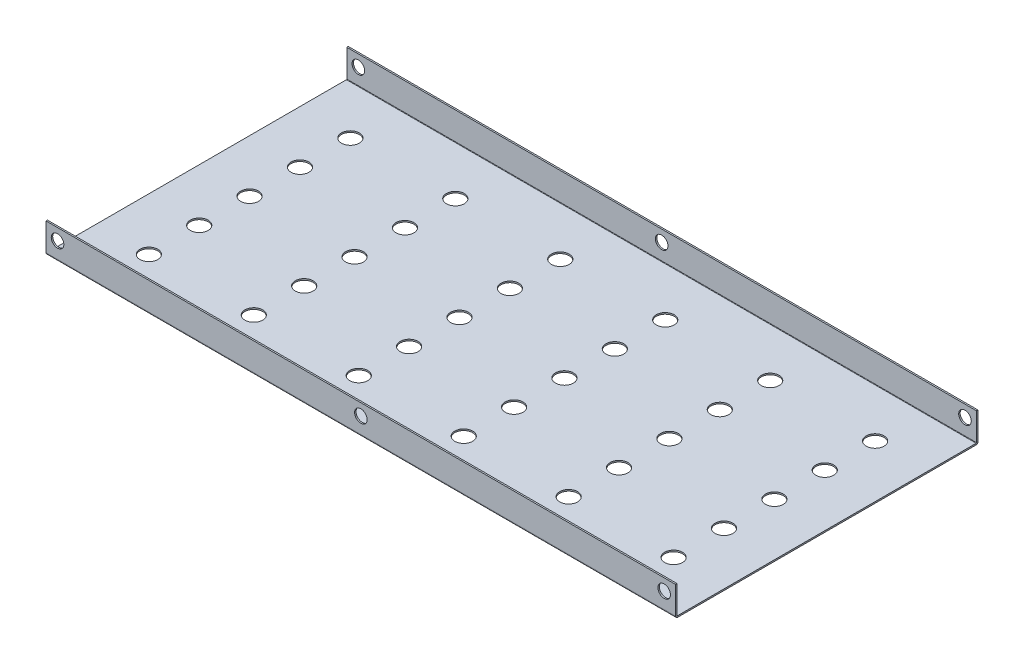
SolidWorks part; units mm, degrees
note: The reader was unsure of these and kept them because the rebuilt part matched: flange length of "边线-法兰1".
material "1023 碳钢板 (SS)"
ref_plane "前视基准面" through (0, 0, 0) normal (0, 0, 1) x (1, 0, 0)
ref_plane "上视基准面" through (0, 0, 0) normal (0, 1, 0) x (1, 0, 0)
ref_plane "右视基准面" through (0, 0, 0) normal (1, 0, 0) x (0, 0, -1)
sketch "草图1" plane through (0, 0, 0) normal (0, 1, 0) x (1, 0, 0)
  line L0 (-100, 72) -> (-100, -72) construction
  line L1 (-150, 72) -> (150, 72)
  line L2 (-150, 72) -> (-150, -72)
  line L3 (-150, -72) -> (150, -72)
  line L5 (-150, -72) -> (150, 72) construction
  line L6 (-150, 72) -> (150, -72) construction
  line L7 (-50, 72) -> (-50, -72) construction
  line L8 (0, 0) -> (0, -72) construction
  line L10 (150, 72) -> (150, -72)
  circle A0 centre (-125, -48) radius 4.25
  circle A1 centre (-125, -24) radius 4.25
  circle A2 centre (-125, 0) radius 4.25
  circle A3 centre (-125, 24) radius 4.25
  circle A4 centre (-125, 48) radius 4.25
  circle A5 centre (-75, -48) radius 4.25
  circle A6 centre (-75, -24) radius 4.25
  circle A7 centre (-75, 0) radius 4.25
  circle A8 centre (-75, 24) radius 4.25
  circle A9 centre (-75, 48) radius 4.25
  circle A40 centre (-25, -48) radius 4.25
  circle A41 centre (-25, -24) radius 4.25
  circle A42 centre (-25, 0) radius 4.25
  circle A43 centre (-25, 24) radius 4.25
  circle A44 centre (-25, 48) radius 4.25
  circle A45 centre (25, -48) radius 4.25
  circle A46 centre (25, -24) radius 4.25
  circle A47 centre (25, 0) radius 4.25
  circle A48 centre (25, 24) radius 4.25
  circle A49 centre (25, 48) radius 4.25
  circle A50 centre (75, 48) radius 4.25
  circle A51 centre (75, 24) radius 4.25
  circle A52 centre (75, 0) radius 4.25
  circle A53 centre (75, -24) radius 4.25
  circle A54 centre (75, -48) radius 4.25
  circle A55 centre (125, -48) radius 4.25
  circle A56 centre (125, -24) radius 4.25
  circle A57 centre (125, 0) radius 4.25
  circle A58 centre (125, 24) radius 4.25
  circle A59 centre (125, 48) radius 4.25
  point P0 (0, 0)
  dimension "D5" = 8.5
  dimension "D6" = 24
  dimension "D11" = 25
  dimension "D18" = 300
  dimension "D2" = 144
  dimension "D3" = 24
  dimension "D4" = 25
  dimension "D7" = 24
  dimension "D8" = 24
  dimension "D9" = 24
  dimension "D10" = 24
  dimension "D12" = 25
  dimension "D13" = 25
  dimension "D14" = 25
  dimension "D15" = 50
  dimension "D16" = 50
base flange "基体-法兰1" sketch "草图1" thickness 0.7 reverse thickness direction no parameters "D1"=0.2
edge flange "边线-法兰1" sketch "草图12" flange profiles "草图12", "草图13" flange angle 90 flange length 14 flange position material inside bend radius 0.2 thickness 0.7 relief rectangular parameters "D6"=10, "D8"=1
sketch "草图12" plane through (0, 0, 72) normal (0, 0, 1) x (1, 0, 0)
  line L2 (-150, 0) -> (-150, 13.3)
  line L3 (-150, 13.3) -> (150, 13.3)
  line L4 (150, 13.3) -> (150, 0)
  line L11 (-150, 0) -> (150, 0) construction
  line L12 (-150, 0) -> (150, 0)
sketch "草图13" plane through (0, 0, -72) normal (0, 0, -1) x (-1, 0, 0)
  line L2 (-150, 0) -> (-150, 13.3)
  line L3 (-150, 13.3) -> (150, 13.3)
  line L4 (150, 13.3) -> (150, 0)
  line L7 (-150, 0) -> (150, 0) construction
  line L8 (-150, 0) -> (150, 0)
bend "边线折弯1" bend radius 0.2 bend angle 90 parameters "D5"=1
bend "边线折弯2" bend radius 0.2 bend angle 90 parameters "D5"=2
sketch "草图14" plane through (0, 0, 71.3) normal (0, 0, -1) x (-1, 0, 0)
  line L0 (0, 13.3) -> (0, 0) construction
  line L1 (150, 13.3) -> (-150, 13.3) construction
  line L2 (-150, 13.3) -> (-150, 0.2) construction
  circle A0 centre (-144.5, 7.8) radius 3
  circle A1 centre (0, 7.8) radius 3
  circle A2 centre (144.5, 7.8) radius 3
  dimension "D1" = 6
  dimension "D2" = 5.5
  dimension "D3" = 5.5
  dimension "D4" = 5.5
  dimension "D5" = 6
extrude "切除-拉伸1" cut sketch "草图14" against normal blind 10
sketch "草图15" plane through (0, 0, -72) normal (0, 0, -1) x (-1, 0, 0)
  line L0 (0, 13.3) -> (0, 0) construction
  line L1 (150, 13.3) -> (-150, 13.3) construction
  line L2 (-150, 13.3) -> (-150, 0.2) construction
  circle A0 centre (-144.5, 7.8) radius 3
  circle A1 centre (0, 7.8) radius 3
  circle A2 centre (144.5, 7.8) radius 3
  dimension "D1" = 6
  dimension "D2" = 5.5
  dimension "D3" = 6
  dimension "D4" = 5.5
  dimension "D5" = 5.5
extrude "切除-拉伸2" cut sketch "草图15" against normal blind 10
sketch "折弯-线1" [suppressed] plane through (0, 0, 0) normal (0, 1, 0) x (1, 0, 0)
sketch "边界框1" [suppressed] plane through (0, 0, 0) normal (0, 1, 0) x (1, 0, 0)
sheet metal parameters "钣金6" thickness 0.7 parameters "D1"=0.2
flat pattern "平板型式6" [suppressed]
sketch "折弯-线2" plane through (0, 0, 0) normal (0, 1, 0) x (1, 0, 0)
sketch3d "边界框2" [suppressed]
  line L0 (200, -72, 0) -> (-200, -72, 0) construction
  line L1 (200, 72, 0) -> (-200, 72, 0) construction
  line L2 (200, -72, 0) -> (200, 72, 0) construction
  line L3 (-200, -72, 0) -> (-200, 72, 0) construction
sheet metal parameters "钣金7" thickness 0.7 parameters "D1"=0.2
flat pattern "平板型式6" [suppressed]
sketch "折弯-线2" plane through (0, 0, 0) normal (0, 1, 0) x (1, 0, 0)
sketch3d "边界框2" [suppressed]
  line L0 (200, -72, 0) -> (-200, -72, 0) construction
  line L1 (200, 72, 0) -> (-200, 72, 0) construction
  line L2 (200, -72, 0) -> (200, 72, 0) construction
  line L3 (-200, -72, 0) -> (-200, 72, 0) construction
bend of the flat pattern "展平-<边线折弯1>1"
bend of the flat pattern "展平-<边线折弯2>1"
sheet metal parameters "钣金8" thickness 0.7 parameters "D1"=0.2
flat pattern "平板型式6" [suppressed]
sketch "折弯-线2" plane through (0, 0, 0) normal (0, 1, 0) x (1, 0, 0)
sketch3d "边界框2" [suppressed]
  line L0 (200, -72, 0) -> (-200, -72, 0) construction
  line L1 (200, 72, 0) -> (-200, 72, 0) construction
  line L2 (200, -72, 0) -> (200, 72, 0) construction
  line L3 (-200, -72, 0) -> (-200, 72, 0) construction
bend of the flat pattern "展平-<边线折弯1>1"
bend of the flat pattern "展平-<边线折弯2>1"
sheet metal parameters "钣金9" thickness 0.7 parameters "D1"=0.2
flat pattern "平板型式6" [suppressed]
sketch "折弯-线2" plane through (0, 0, 0) normal (0, 1, 0) x (1, 0, 0)
sketch3d "边界框2" [suppressed]
  line L0 (200, -72, 0) -> (-200, -72, 0) construction
  line L1 (200, 72, 0) -> (-200, 72, 0) construction
  line L2 (200, -72, 0) -> (200, 72, 0) construction
  line L3 (-200, -72, 0) -> (-200, 72, 0) construction
bend of the flat pattern "展平-<边线折弯1>1"
bend of the flat pattern "展平-<边线折弯2>1"
